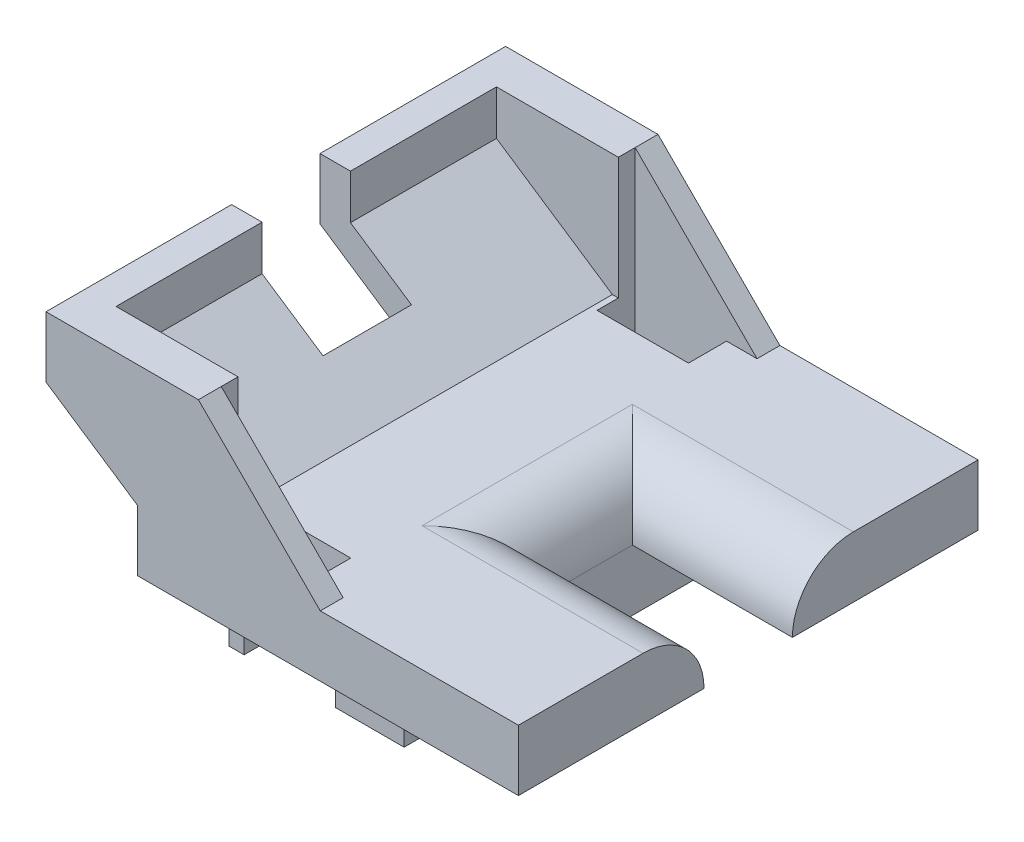
SolidWorks part; units mm, degrees
material "ABS"
ref_plane "Front" through (0, 0, 0) normal (0, 0, 1) x (1, 0, 0)
ref_plane "Top" through (0, 0, 0) normal (0, 1, 0) x (1, 0, 0)
ref_plane "Right" through (0, 0, 0) normal (1, 0, 0) x (0, 0, -1)
sketch "Sketch1" plane through (0, 0, 0) normal (0, 1, 0) x (1, 0, 0)
  line L0 (3.125, 3.77) -> (3.125, 0.725)
  line L1 (-3.125, -3.77) -> (3.125, -3.77)
  line L2 (-3.125, -3.77) -> (-3.125, 3.77)
  line L3 (-3.125, 3.77) -> (3.125, 3.77)
  line L4 (3.125, -3.77) -> (3.125, 3.77) construction
  line L5 (-3.125, -3.77) -> (3.125, 3.77) construction
  line L6 (-3.125, 3.77) -> (3.125, -3.77) construction
  line L7 (0.5, -0.725) -> (3.125, -0.725)
  line L8 (0.5, -0.725) -> (0.5, 0.725)
  line L9 (0.5, 0.725) -> (3.125, 0.725)
  line L10 (3.125, -0.725) -> (3.125, 0.725) construction
  line L11 (0.5, -0.725) -> (3.125, 0.725) construction
  line L12 (0.5, 0.725) -> (3.125, -0.725) construction
  line L13 (3.125, -0.725) -> (3.125, -3.77)
  line L14 (1.8125, 0) -> (0, 0) construction
  line L15 (3.075, 3.77) -> (3.075, -3.77) construction
  point P0 (0, 0)
  point P6 (1.8125, 0)
  dimension "D1" = 7.54
  dimension "D2" = 6.25
  dimension "D3" = 1.45
  dimension "D4" = 2.575
  dimension "D5" = 6.2
extrude "Base" add sketch "Sketch1" along normal blind 1
fillet "Slot Guide Fillet (1mm)" radius 1 3 edges at (1.8125, 1, 0.725) (0.5, 1, 0) (1.8125, 1, -0.725)
sketch "Sketch2" plane through (0, 0, -3.77) normal (0, 0, -1) x (-1, 0, 0)
  line L0 (3.125, 1) -> (0.125, 1)
  line L1 (-3.125, 1) -> (3.125, 1) construction
  line L2 (0.125, 1) -> (2.125, 3)
  line L3 (2.125, 3) -> (4.625, 3)
  line L4 (4.625, 3) -> (4.625, 2)
  line L5 (4.625, 2) -> (3.125, 1)
  line L6 (3.125, 1) -> (3.125, 0) construction
  dimension "D1" = 1
  dimension "D2" = 2
  dimension "D3" = 1.5
  dimension "D4" = 2.5
  dimension "D5" = 3
extrude "Side Wall 1" add sketch "Sketch2" against normal blind 0.65
mirror "Side Wall 2" about plane through (0, 0, 0) normal (0, 0, 1) of "Side Wall 1"
sketch "Sketch3" plane through (0, 0, -3.12) normal (0, 0, 1) x (1, 0, 0)
  line L0 (-3.125, 1) -> (-4.625, 2)
  line L1 (-4.625, 2) -> (-4.625, 3)
  line L2 (-4.625, 3) -> (-4.125, 3)
  line L3 (-4.625, 3) -> (-2.125, 3) construction
  line L4 (-4.125, 3) -> (-4.125, 2.2676)
  line L5 (-4.125, 2.2676) -> (-2.2236, 1)
  line L6 (-0.125, 1) -> (-3.125, 1) construction
  line L7 (-2.2236, 1) -> (-3.125, 1)
  dimension "D1" = 0.5
  dimension "D2" = 0.5
extrude "Wall Link" add sketch "Sketch3" along normal up to surface (6.24 mm away) up to face at (-2.925, 2, 3.12)
sketch "Sketch4" plane through (0, 0, 0) normal (0, -1, 0) x (1, 0, 0)
  line L0 (-0.9375, 0) -> (0, 0) construction
  line L1 (-2.375, -3.02) -> (0.5, -3.02)
  line L2 (-2.375, -3.02) -> (-2.375, 3.02)
  line L3 (-2.375, 3.02) -> (0.5, 3.02)
  line L4 (0.5, -3.02) -> (0.5, 3.02)
  line L5 (-2.375, -3.02) -> (0.5, 3.02) construction
  line L6 (-2.375, 3.02) -> (0.5, -3.02) construction
  line L7 (0.5, 0.725) -> (0.5, -0.725) construction
  line L8 (-3.125, 3.77) -> (3.125, 3.77) construction
  line L9 (-3.125, -3.77) -> (-3.125, 3.77) construction
  point P0 (-0.9375, 0)
  dimension "D1" = 0.75
  dimension "D2" = 0.75
extrude "Lower Fit" add sketch "Sketch4" along normal blind 1
sketch "Sketch5" plane through (0, 3, 0) normal (0, 1, 0) x (1, 0, 0)
  line L0 (-4.625, -3.77) -> (-4.625, 3.77) construction
  line L1 (-4.625, 0.725) -> (-3.125, 0.725)
  line L2 (-4.625, 0.725) -> (-4.625, -0.725)
  line L3 (-4.625, -0.725) -> (-3.125, -0.725)
  line L4 (-3.125, 0.725) -> (-3.125, -0.725)
  line L5 (0.5, 0.725) -> (3.125, 0.725) construction
  line L6 (3.125, -0.725) -> (0.5, -0.725) construction
  line L7 (-3.125, 3.77) -> (-3.125, -3.77) construction
  line L8 (-4.625, 0) -> (0, 0) construction
  line L9 (-0.625, -3.395) -> (-0.625, -2.77)
  line L10 (-2.125, 3.395) -> (-0.625, 3.395)
  line L11 (-2.125, 3.395) -> (-2.125, 2.77)
  line L12 (-2.125, 2.77) -> (-0.625, 2.77)
  line L13 (-0.625, 3.395) -> (-0.625, 2.77)
  line L14 (-2.125, -2.77) -> (-0.625, -2.77)
  line L15 (-2.125, -3.395) -> (-2.125, -2.77)
  line L16 (-2.125, -3.395) -> (-0.625, -3.395)
  line L17 (-2.125, 3.77) -> (-0.125, 3.77) construction
  line L18 (-2.125, 3.12) -> (-2.125, 3.77) construction
  line L19 (-0.125, 3.12) -> (-0.125, 3.77) construction
  dimension "D1" = 1
  dimension "D2" = 0.375
  dimension "D3" = 0.5
extrude "Cut Through" cut sketch "Sketch5" against normal up to surface (4 mm away) up to face at (-0.9375, -1, 0)
sketch "Sketch6" plane through (0, 1, 0) normal (0, 1, 0) x (1, 0, 0)
  line L1 (-0.125, 3.12) -> (-0.625, 3.12)
  line L2 (-0.125, 3.12) -> (-0.125, 3.395)
  line L3 (-0.125, 3.395) -> (-0.625, 3.395)
  line L4 (-0.625, 3.12) -> (-0.625, 3.395)
  line L5 (-0.125, -3.12) -> (-0.625, -3.12)
  line L6 (-0.125, -3.12) -> (-0.125, -3.395)
  line L7 (-0.125, -3.395) -> (-0.625, -3.395)
  line L8 (-0.625, -3.12) -> (-0.625, -3.395)
extrude "Cut Through Finish" cut sketch "Sketch6" along normal up to surface (2 mm away) up to face at (-3.4107, 3, -2.6607)
sketch "Sketch7" plane through (0, 0, 0) normal (0, 0, 1) x (1, 0, 0)
  line L0 (-3.125, -3) -> (-2.375, -3)
  line L1 (-3.125, 0) -> (3.125, 0) construction
  line L2 (-3.125, 1) -> (-3.125, 0) construction
  line L3 (-3.125, -3) -> (-4.125, -2)
  line L4 (-4.125, -2) -> (-4.125, -1)
  line L5 (-4.125, -1) -> (-3.375, -1)
  line L6 (-3.125, 0) -> (-3.125, -0.75)
  line L7 (-3.125, 0) -> (-2.375, 0)
  line L8 (-2.375, 0) -> (-2.375, -1)
  line L9 (-2.375, -1) -> (-2.375, -3)
  arc A0 (-3.125, -0.75) -> (-3.375, -1) centre (-3.375, -0.75) cw
  dimension "D5" = 0.25
  dimension "D1" = 3
  dimension "D2" = 1
  dimension "D3" = 1
  dimension "D4" = 1
extrude "Rear Insert" add sketch "Sketch7" along normal mid plane 1.45
